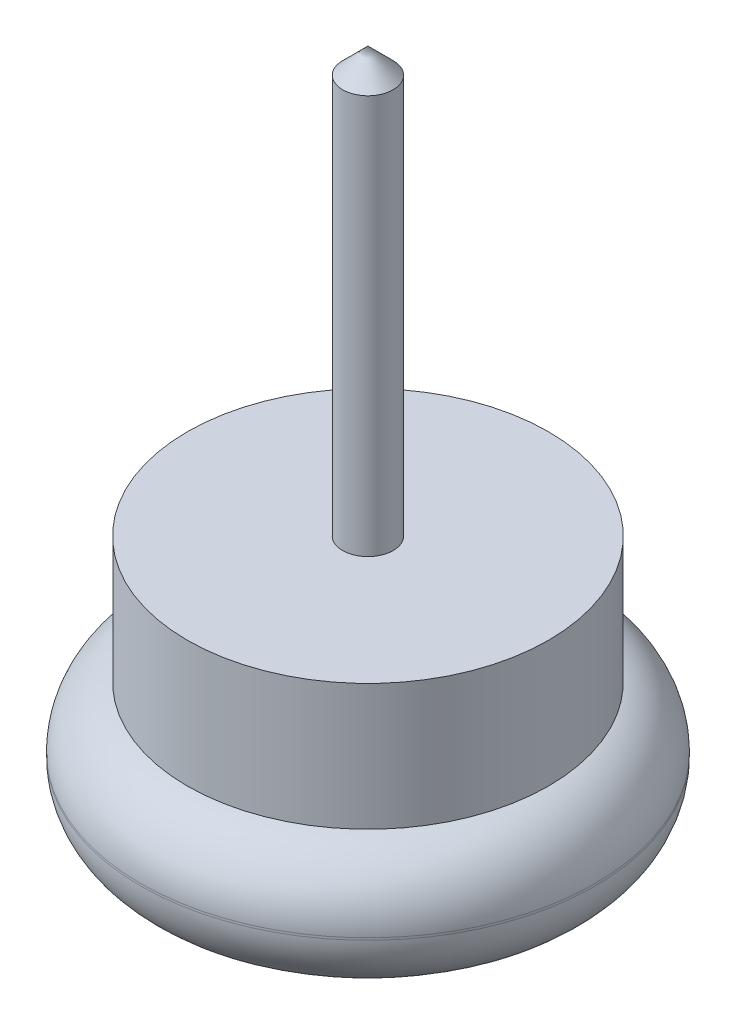
SolidWorks part; units mm, degrees
ref_plane "Front Plane" through (0, 0, 0) normal (0, 0, 1) x (1, 0, 0)
ref_plane "Top Plane" through (0, 0, 0) normal (0, 1, 0) x (1, 0, 0)
ref_plane "Right Plane" through (0, 0, 0) normal (1, 0, 0) x (0, 0, -1)
sketch "Sketch1" plane through (0, 0, 0) normal (0, 1, 0) x (1, 0, 0)
  circle A0 centre (0, 0) radius 9
  dimension "D1" = 18
extrude "Boss-Extrude1" add sketch "Sketch1" along normal blind 5
sketch "Sketch2" plane through (0, 5, 0) normal (0, 1, 0) x (1, 0, 0)
  circle A0 centre (0, 0) radius 7.15
  dimension "D1" = 14.3
extrude "Boss-Extrude2" add sketch "Sketch2" along normal blind 5
sketch "Sketch3" plane through (0, 10, 0) normal (0, 1, 0) x (1, 0, 0)
  circle A0 centre (0, 0) radius 1
  dimension "D1" = 2
extrude "Boss-Extrude3" add sketch "Sketch3" along normal blind 16.8
fillet "Fillet1" radius 2.5 2 edges at (0, 5, 9) (0, 0, 9)
chamfer "Chamfer1" distance 1 angle 45 1 edges at (0, 26.8, 1)
